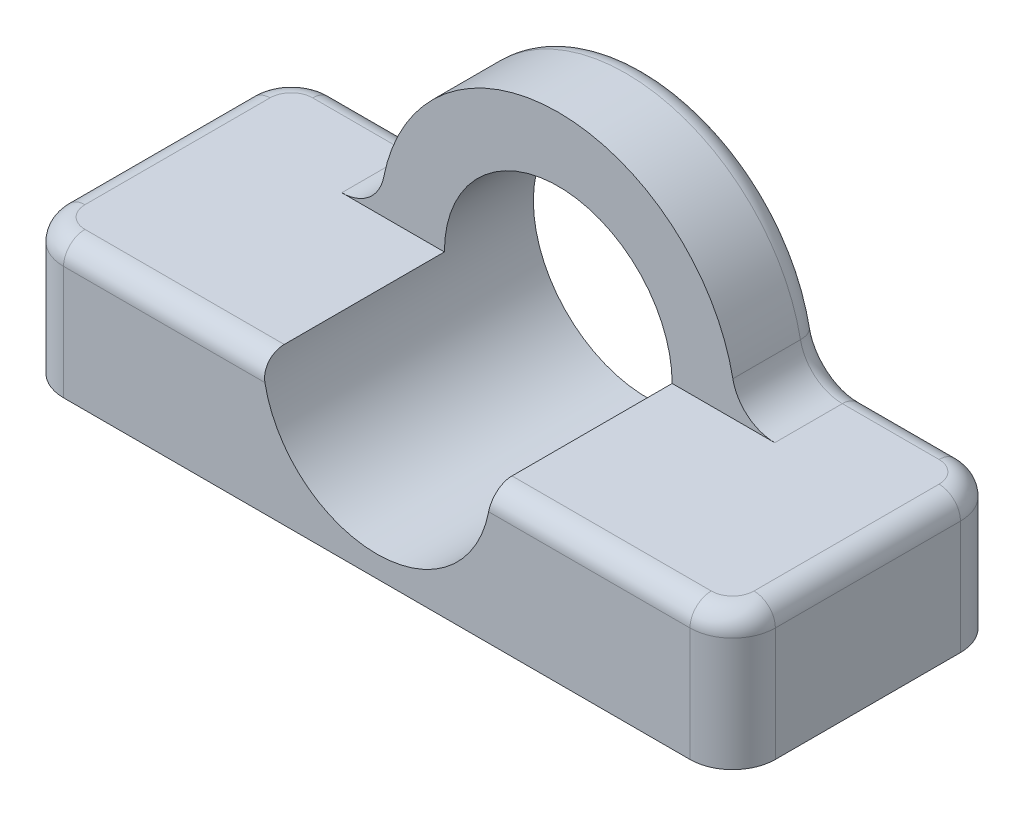
SolidWorks part; units mm, degrees
ref_plane "Front" through (0, 0, 0) normal (0, 0, 1) x (1, 0, 0)
ref_plane "Top" through (0, 0, 0) normal (0, 1, 0) x (1, 0, 0)
ref_plane "Right" through (0, 0, 0) normal (1, 0, 0) x (0, 0, -1)
sketch "Sketch1" plane through (0, 0, 0) normal (0, 1, 0) x (1, 0, 0)
  line L1 (0, 0) -> (100, 0)
  line L2 (0, 0) -> (0, 38)
  line L3 (0, 38) -> (100, 38)
  line L4 (100, 0) -> (100, 38)
  dimension "D1" = 100
  dimension "D2" = 38
extrude "Base-Extrude" add sketch "Sketch1" along normal blind 19
ref_plane "Plane1" through (50, 0, 0) normal (-1, 0, 0) x (0, 0, 1)
sketch "Sketch2" plane through (0, 0, -38) normal (0, 0, -1) x (-1, 0, 0)
  line L0 (-100, 19) -> (0, 19) construction
  line L1 (-25, 19) -> (-75, 19)
  arc A0 (-75, 19) -> (-25, 19) centre (-50, 19) cw
  dimension "D1" = 50
extrude "Boss-Extrude1" add sketch "Sketch2" against normal blind 12.5
fillet "Fillet1" radius 6 2 edges at (75, 19, -31.75) (25, 19, -31.75)
sketch "Sketch3" plane through (0, 0, -38) normal (0, 0, -1) x (-1, 0, 0)
  circle A0 centre (-50, 19) radius 16
  dimension "D1" = 32
extrude "Cut-Extrude1" cut sketch "Sketch3" against normal through all
fillet "Fillet2" radius 6 4 edges at (0, 9.5, -38) (100, 9.5, -38) (100, 9.5, 0) (0, 9.5, 0)
fillet "Fillet3" radius 3 13 edges at (50, 44, -38) (12.7931, 19, -38) (76.6038, 20.3649, -38) (23.3962, 20.3649, -38) (80, 19, 0) (100, 19, -19) (20, 19, 0) (87.2069, 19, -38) (98.2426, 19, -36.2426) (98.2426, 19, -1.7574) (0, 19, -19) (1.7574, 19, -1.7574) (1.7574, 19, -36.2426)
